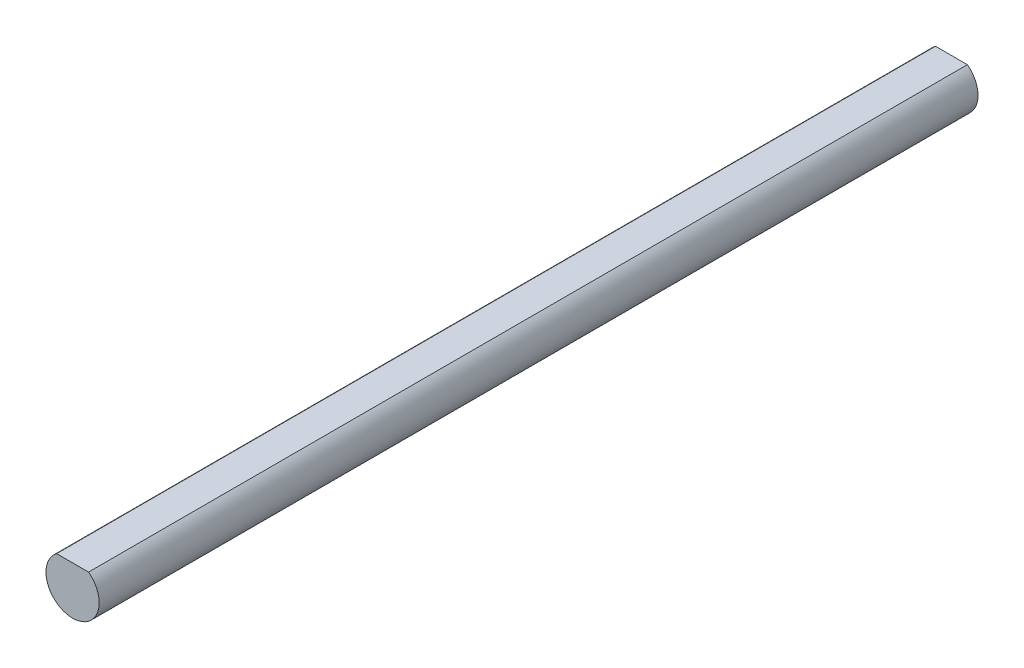
SolidWorks part; units mm, degrees
ref_plane "Front Plane" through (0, 0, 0) normal (0, 0, 1) x (1, 0, 0)
ref_plane "Top Plane" through (0, 0, 0) normal (0, 1, 0) x (1, 0, 0)
ref_plane "Right Plane" through (0, 0, 0) normal (1, 0, 0) x (0, 0, -1)
sketch "Sketch1" plane through (0, 0, 0) normal (0, 0, 1) x (1, 0, 0)
  line L0 (-1.5, 2) -> (1.5, 2)
  arc A0 (-1.5, 2) -> (1.5, 2) centre (0, 0) ccw
  dimension "D1" = 5
  dimension "D2" = 2
extrude "Boss-Extrude1" add sketch "Sketch1" along normal blind 82.55
